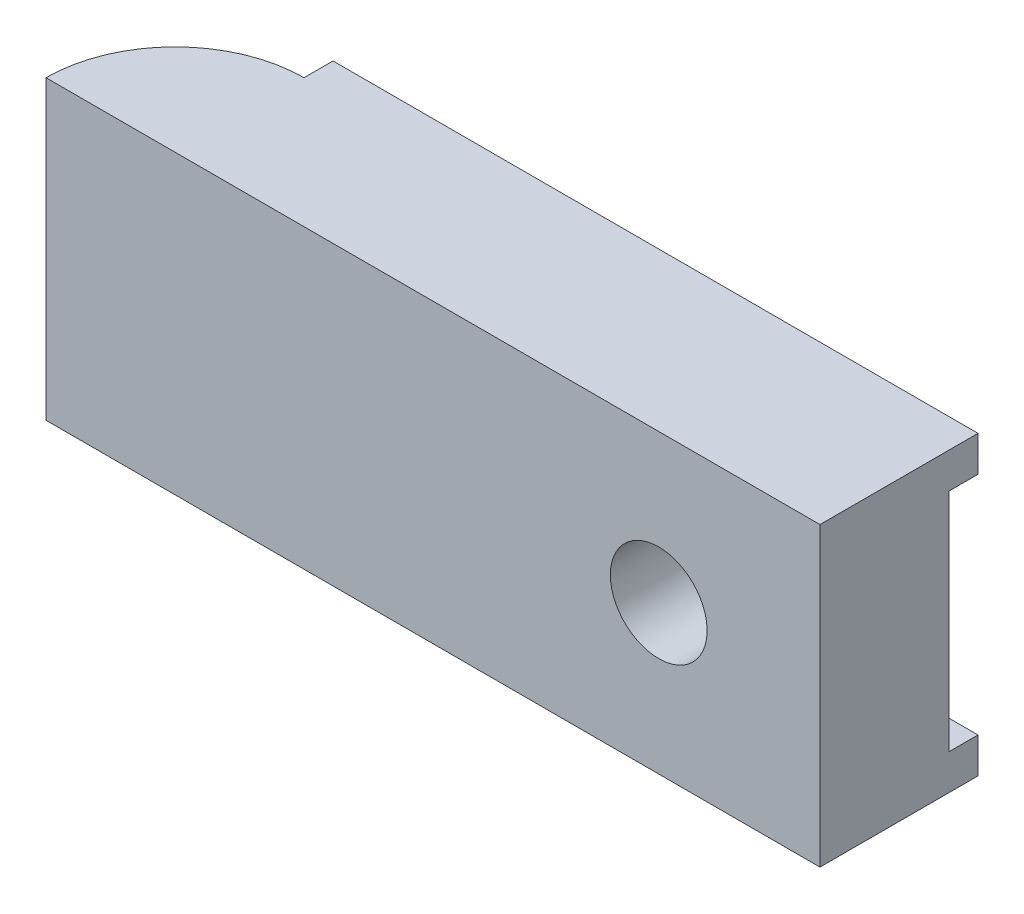
SolidWorks part; units mm, degrees
other "Câmera1"
ref_plane "Plano frontal" through (0, 0, 0) normal (0, 0, 1) x (1, 0, 0)
ref_plane "Plano superior" through (0, 0, 0) normal (0, 1, 0) x (1, 0, 0)
ref_plane "Plano direito" through (0, 0, 0) normal (1, 0, 0) x (0, 0, -1)
sketch "Esboço4" plane through (0, 0, 0) normal (0, 1, 0) x (1, 0, 0)
  line L0 (-19.2, 2.35) -> (-19.2, 1.65)
  line L1 (-20, -2.45) -> (20, -2.45)
  line L2 (-20, -2.45) -> (-20, 2.35)
  line L3 (-19.9, 2.45) -> (-19.3, 2.45)
  line L4 (20, -2.45) -> (20, 2.35)
  line L5 (-19.1, 1.55) -> (-18.1, 1.55)
  line L6 (19.2, 2.35) -> (19.2, 1.65)
  line L7 (19.3, 2.45) -> (19.9, 2.45)
  line L8 (-18, 1.65) -> (-18, 2.35)
  line L9 (-17.9, 2.45) -> (-17.3, 2.45)
  line L10 (-17.2, 2.35) -> (-17.2, 1.65)
  line L11 (-16, 1.65) -> (-16, 2.35)
  line L12 (-15.9, 2.45) -> (-15.3, 2.45)
  line L13 (-15.2, 2.35) -> (-15.2, 1.65)
  line L14 (-14, 1.65) -> (-14, 2.35)
  line L15 (-13.9, 2.45) -> (-13.3, 2.45)
  line L16 (-13.2, 2.35) -> (-13.2, 1.65)
  line L17 (-12, 1.65) -> (-12, 2.35)
  line L18 (-11.9, 2.45) -> (-11.3, 2.45)
  line L19 (-11.2, 2.35) -> (-11.2, 1.65)
  line L20 (-10, 1.65) -> (-10, 2.35)
  line L21 (-9.9, 2.45) -> (-9.3, 2.45)
  line L22 (-9.2, 2.35) -> (-9.2, 1.65)
  line L23 (-8, 1.65) -> (-8, 2.35)
  line L24 (-7.9, 2.45) -> (-7.3, 2.45)
  line L25 (-7.2, 2.35) -> (-7.2, 1.65)
  line L26 (-7.1, 1.55) -> (7.1, 1.55)
  line L27 (-9.1, 1.55) -> (-8.1, 1.55)
  line L28 (-11.1, 1.55) -> (-10.1, 1.55)
  line L29 (-13.1, 1.55) -> (-12.1, 1.55)
  line L30 (-15.1, 1.55) -> (-14.1, 1.55)
  line L31 (-17.1, 1.55) -> (-16.1, 1.55)
  line L32 (17.2, 2.35) -> (17.2, 1.65)
  line L33 (17.3, 2.45) -> (17.9, 2.45)
  line L34 (18, 1.65) -> (18, 2.35)
  line L35 (15.2, 2.35) -> (15.2, 1.65)
  line L36 (15.3, 2.45) -> (15.9, 2.45)
  line L37 (16, 1.65) -> (16, 2.35)
  line L38 (13.2, 2.35) -> (13.2, 1.65)
  line L39 (13.3, 2.45) -> (13.9, 2.45)
  line L40 (14, 1.65) -> (14, 2.35)
  line L41 (11.2, 2.35) -> (11.2, 1.65)
  line L42 (11.3, 2.45) -> (11.9, 2.45)
  line L43 (12, 1.65) -> (12, 2.35)
  line L44 (9.2, 2.35) -> (9.2, 1.65)
  line L45 (9.3, 2.45) -> (9.9, 2.45)
  line L46 (10, 1.65) -> (10, 2.35)
  line L47 (7.2, 2.35) -> (7.2, 1.65)
  line L48 (7.3, 2.45) -> (7.9, 2.45)
  line L49 (8, 1.65) -> (8, 2.35)
  line L50 (8.1, 1.55) -> (9.1, 1.55)
  line L51 (10.1, 1.55) -> (11.1, 1.55)
  line L52 (12.1, 1.55) -> (13.1, 1.55)
  line L53 (14.1, 1.55) -> (15.1, 1.55)
  line L54 (16.1, 1.55) -> (17.1, 1.55)
  line L55 (18.1, 1.55) -> (19.1, 1.55)
  arc A0 (19.9, 2.45) -> (20, 2.35) centre (19.9, 2.35) cw
  arc A1 (19.2, 2.35) -> (19.3, 2.45) centre (19.3, 2.35) cw
  arc A2 (19.1, 1.55) -> (19.2, 1.65) centre (19.1, 1.65) ccw
  arc A3 (18.1, 1.55) -> (18, 1.65) centre (18.1, 1.65) cw
  arc A4 (17.9, 2.45) -> (18, 2.35) centre (17.9, 2.35) cw
  arc A5 (17.2, 2.35) -> (17.3, 2.45) centre (17.3, 2.35) cw
  arc A6 (17.2, 1.65) -> (17.1, 1.55) centre (17.1, 1.65) cw
  arc A7 (16.1, 1.55) -> (16, 1.65) centre (16.1, 1.65) cw
  arc A8 (15.9, 2.45) -> (16, 2.35) centre (15.9, 2.35) cw
  arc A9 (15.2, 2.35) -> (15.3, 2.45) centre (15.3, 2.35) cw
  arc A10 (15.2, 1.65) -> (15.1, 1.55) centre (15.1, 1.65) cw
  arc A11 (14, 1.65) -> (14.1, 1.55) centre (14.1, 1.65) ccw
  arc A12 (13.9, 2.45) -> (14, 2.35) centre (13.9, 2.35) cw
  arc A13 (13.2, 2.35) -> (13.3, 2.45) centre (13.3, 2.35) cw
  arc A14 (13.2, 1.65) -> (13.1, 1.55) centre (13.1, 1.65) cw
  arc A15 (12, 1.65) -> (12.1, 1.55) centre (12.1, 1.65) ccw
  arc A16 (11.9, 2.45) -> (12, 2.35) centre (11.9, 2.35) cw
  arc A17 (11.2, 2.35) -> (11.3, 2.45) centre (11.3, 2.35) cw
  arc A18 (11.2, 1.65) -> (11.1, 1.55) centre (11.1, 1.65) cw
  arc A19 (10, 1.65) -> (10.1, 1.55) centre (10.1, 1.65) ccw
  arc A20 (9.9, 2.45) -> (10, 2.35) centre (9.9, 2.35) cw
  arc A21 (9.2, 2.35) -> (9.3, 2.45) centre (9.3, 2.35) cw
  arc A22 (9.2, 1.65) -> (9.1, 1.55) centre (9.1, 1.65) cw
  arc A23 (8, 1.65) -> (8.1, 1.55) centre (8.1, 1.65) ccw
  arc A24 (7.9, 2.45) -> (8, 2.35) centre (7.9, 2.35) cw
  arc A25 (7.2, 2.35) -> (7.3, 2.45) centre (7.3, 2.35) cw
  arc A26 (7.2, 1.65) -> (7.1, 1.55) centre (7.1, 1.65) cw
  arc A27 (-7.2, 1.65) -> (-7.1, 1.55) centre (-7.1, 1.65) ccw
  arc A28 (-7.3, 2.45) -> (-7.2, 2.35) centre (-7.3, 2.35) cw
  arc A29 (-8, 1.65) -> (-8.1, 1.55) centre (-8.1, 1.65) cw
  arc A30 (-8, 2.35) -> (-7.9, 2.45) centre (-7.9, 2.35) cw
  arc A31 (-9.2, 1.65) -> (-9.1, 1.55) centre (-9.1, 1.65) ccw
  arc A32 (-9.3, 2.45) -> (-9.2, 2.35) centre (-9.3, 2.35) cw
  arc A33 (-10, 2.35) -> (-9.9, 2.45) centre (-9.9, 2.35) cw
  arc A34 (-10, 1.65) -> (-10.1, 1.55) centre (-10.1, 1.65) cw
  arc A35 (-11.2, 1.65) -> (-11.1, 1.55) centre (-11.1, 1.65) ccw
  arc A36 (-11.3, 2.45) -> (-11.2, 2.35) centre (-11.3, 2.35) cw
  arc A37 (-12, 1.65) -> (-12.1, 1.55) centre (-12.1, 1.65) cw
  arc A38 (-12, 2.35) -> (-11.9, 2.45) centre (-11.9, 2.35) cw
  arc A39 (-13.2, 1.65) -> (-13.1, 1.55) centre (-13.1, 1.65) ccw
  arc A40 (-13.3, 2.45) -> (-13.2, 2.35) centre (-13.3, 2.35) cw
  arc A41 (-14, 1.65) -> (-14.1, 1.55) centre (-14.1, 1.65) cw
  arc A42 (-14, 2.35) -> (-13.9, 2.45) centre (-13.9, 2.35) cw
  arc A43 (-15.2, 1.65) -> (-15.1, 1.55) centre (-15.1, 1.65) ccw
  arc A44 (-15.3, 2.45) -> (-15.2, 2.35) centre (-15.3, 2.35) cw
  arc A45 (-16, 1.65) -> (-16.1, 1.55) centre (-16.1, 1.65) cw
  arc A46 (-16, 2.35) -> (-15.9, 2.45) centre (-15.9, 2.35) cw
  arc A47 (-17.2, 1.65) -> (-17.1, 1.55) centre (-17.1, 1.65) ccw
  arc A48 (-17.3, 2.45) -> (-17.2, 2.35) centre (-17.3, 2.35) cw
  arc A49 (-18, 1.65) -> (-18.1, 1.55) centre (-18.1, 1.65) cw
  arc A50 (-18, 2.35) -> (-17.9, 2.45) centre (-17.9, 2.35) cw
  arc A51 (-19.2, 1.65) -> (-19.1, 1.55) centre (-19.1, 1.65) ccw
  arc A52 (-19.2, 2.35) -> (-19.3, 2.45) centre (-19.3, 2.35) ccw
  arc A53 (-20, 2.35) -> (-19.9, 2.45) centre (-19.9, 2.35) cw
  point P0 (0, 0)
  point P62 (19.2, 2.45)
  point P83 (14, 1.55)
  point P92 (12, 1.55)
  point P101 (10, 1.55)
  point P110 (8, 1.55)
  dimension "D2" = 0.1
  dimension "D1" = 7
extrude "Ressalto-extrusão2" add sketch "Esboço4" along normal blind 9.2
sketch "Esboço5" plane through (0, 0, -1.55) normal (0, 0, -1) x (-1, 0, 0)
  circle A0 centre (0, 4.6) radius 2.15
  dimension "D1" = 4.3
extrude "Corte-extrusão2" cut sketch "Esboço5" against normal blind 9.2
chamfer "Chanfro2" distance 0.3 angle 45 1 edges at (-2.15, 4.6, -1.55)
sketch "Sketch1" plane through (20, 0, 0) normal (1, 0, 0) x (0, 0, -1)
  line L1 (5.7525, 12.1439) -> (-6.2616, 12.1439)
  line L2 (5.7525, 12.1439) -> (5.7525, -5.0794)
  line L3 (5.7525, -5.0794) -> (-6.2616, -5.0794)
  line L4 (-6.2616, 12.1439) -> (-6.2616, -5.0794)
extrude "Cut-Extrude1" cut sketch "Sketch1" against normal blind 25
sketch "Sketch3" plane through (-5, 0, 0) normal (1, 0, 0) x (0, 0, -1)
  line L1 (1.55, 9.2) -> (-2.45, 9.2)
  line L2 (1.55, 9.2) -> (1.55, 0)
  line L3 (1.55, 0) -> (-2.45, 0)
  line L4 (-2.45, 9.2) -> (-2.45, 0)
extrude "Boss-Extrude1" add sketch "Sketch3" along normal blind 5
sketch "Sketch4" plane through (0, 0, -1.55) normal (0, 0, -1) x (-1, 0, 0)
  line L0 (0, 4.6) -> (5, 4.6)
  line L1 (0, 0) -> (0, 9.2) construction
  circle A0 centre (5, 4.6) radius 1.5
  dimension "D1" = 5
extrude "Cut-Extrude3" cut sketch "Sketch4" against normal blind 10 contours A0 region at (-5, 3.1424, -1.55)
sketch "Sketch5" plane through (0, 0, 0) normal (0, -1, 0) x (1, 0, 0)
  line L1 (-33.582, -23.2473) -> (9.0238, -23.2473)
  line L2 (-33.582, -23.2473) -> (-33.582, 10.2625)
  line L3 (-33.582, 10.2625) -> (9.0238, 10.2625)
  line L4 (9.0238, -23.2473) -> (9.0238, 10.2625)
extrude "Cut-Extrude4" cut sketch "Sketch5" against normal blind 1.1
sketch "Sketch6" plane through (0, 9.2, 0) normal (0, 1, 0) x (1, 0, 0)
  line L1 (-34.3682, -9.243) -> (23.8083, -9.243)
  line L2 (-34.3682, -9.243) -> (-34.3682, 16.6451)
  line L3 (-34.3682, 16.6451) -> (23.8083, 16.6451)
  line L4 (23.8083, -9.243) -> (23.8083, 16.6451)
extrude "Cut-Extrude5" cut sketch "Sketch6" against normal blind 1.1
sketch "Sketch7" plane through (0, 8.1, 0) normal (0, 1, 0) x (1, 0, 0)
  line L1 (-20, -2.45) -> (0, -2.45)
  line L2 (-20, -2.45) -> (-20, 2.45)
  line L3 (-20, 2.45) -> (0, 2.45)
  line L4 (0, -2.45) -> (0, 2.45)
  dimension "D1" = 4.9
extrude "Boss-Extrude2" add sketch "Sketch7" along normal blind 1.1
sketch "Sketch8" plane through (0, 1.1, 0) normal (0, -1, 0) x (1, 0, 0)
  line L1 (-20, 2.45) -> (0, 2.45)
  line L2 (-20, 2.45) -> (-20, -2.45)
  line L3 (-20, -2.45) -> (0, -2.45)
  line L4 (0, 2.45) -> (0, -2.45)
  dimension "D1" = 4.9
extrude "Boss-Extrude3" add sketch "Sketch8" along normal blind 1.1
ref_plane "Plane1" through (-24.9, 8.2, -2.45) normal (0, 1, 0) x (1, 0, 0)
sketch "Sketch12" plane through (0, 0, 0) normal (0, -1, 0) x (1, 0, 0)
  line L0 (-20, 2.45) -> (-20, -2.45) construction
  line L1 (-20, 2.45) -> (-24, 2.45)
  line L7 (-20, 2.45) -> (-20, -2.45)
  line L8 (-20, -2.45) -> (0, -2.45)
  line L9 (0, -2.45) -> (0, 2.45)
  line L10 (0, 2.45) -> (-20, 2.45)
  line L11 (-20, 2.45) -> (-20, -1.55)
  arc A0 (-20, -1.55) -> (-24, 2.45) centre (-20, 2.45) cw
  dimension "D1" = 0
extrude "Boss-Extrude5" add sketch "Sketch12" against normal blind 9.2
